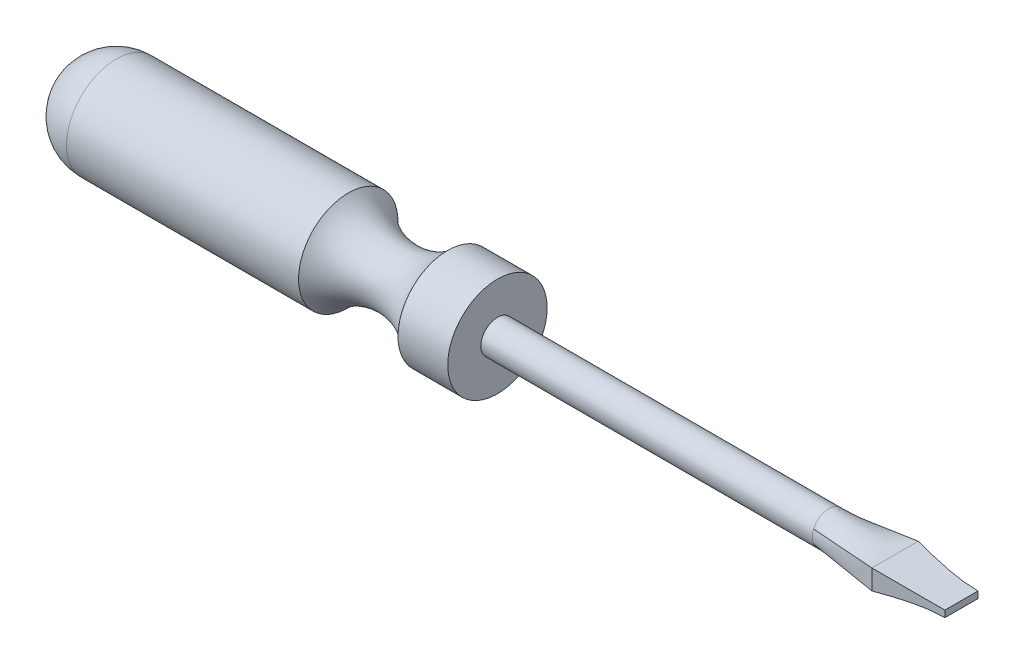
SolidWorks part; units mm, degrees
ref_plane "Front Plane" through (0, 0, 0) normal (1, 0, 0) x (0, 1, 0)
ref_plane "Top Plane" through (0, 0, 0) normal (0, 0, 1) x (0, 1, 0)
ref_plane "Right Plane" through (0, 0, 0) normal (0, 1, 0) x (-1, 0, 0)
sketch "Sketch3" plane through (0, 0, 0) normal (0, 0, 1) x (0, 1, 0)
  line L0 (0, 0) -> (0, 165.1)
  line L1 (19.05, 146.05) -> (19.05, 57.15)
  line L2 (19.05, 19.05) -> (19.05, 0)
  line L3 (19.05, 0) -> (0, 0)
  line L4 (0, 165.1) -> (-19.2923, 165.1) construction
  line L5 (0, 0) -> (0, -127)
  line L6 (0, -127) -> (6.35, -127)
  line L7 (6.35, -127) -> (6.35, 0)
  arc A0 (0, 165.1) -> (19.05, 146.05) centre (0, 146.05) cw
  arc A1 (19.05, 57.15) -> (19.05, 19.05) centre (35.8505, 38.1) ccw
  dimension "D1" = 19.05
  dimension "D4" = 25.4
  dimension "D2" = 38.1
  dimension "D3" = 19.05
  dimension "D5" = 165.1
  dimension "D6" = 6.35
  dimension "D7" = 127
revolve "Revolve2" add sketch "Sketch3" angle 360 about L0 region at (-83.9571, 8.8984, 0)
sketch "Sketch6" plane through (0, 0, 0) normal (1, 0, 0) x (0, 1, 0)
  circle A0 centre (0, 0) radius 19.05 construction
  circle A1 centre (0, 0) radius 19.05
  circle A2 centre (0, 0) radius 6.35
  dimension "D1" = 12.7
ref_plane "Plane3" through (127, 0, 0) normal (1, 0, 0) x (0, 0, -1)
sketch "Sketch7" plane through (127, 0, 0) normal (1, 0, 0) x (0, 0, -1)
  circle A0 centre (0, 0) radius 6.35 construction
  circle A1 centre (0, 0) radius 6.35
  point P3 (0, 0)
ref_plane "Plane1" through (152.4, 0, 0) normal (1, 0, 0) x (0, 0, -1)
ref_plane "Plane2" through (177.8, 0, 0) normal (1, 0, 0) x (0, 0, -1)
sketch "Sketch4" plane through (152.4, 0, 0) normal (1, 0, 0) x (0, 0, -1)
  line L1 (-8.89, 3.81) -> (8.89, 3.81)
  line L2 (-8.89, 3.81) -> (-8.89, -3.81)
  line L3 (-8.89, -3.81) -> (8.89, -3.81)
  line L4 (8.89, 3.81) -> (8.89, -3.81)
  line L5 (-8.89, 3.81) -> (8.89, -3.81) construction
  line L6 (-8.89, -3.81) -> (8.89, 3.81) construction
  circle A2 centre (0, 0) radius 19.05 construction
  circle A3 centre (0, 0) radius 19.05 construction
  point P1 (-0.2403, 7.238)
  point P3 (0, 0)
  point P8 (0, 0)
  point P9 (0, 0)
  point P11 (0, 0)
  point P12 (0, 0)
  point P13 (0, 0)
  dimension "D1" = 7.62
  dimension "D2" = 17.78
sketch "Sketch5" plane through (177.8, 0, 0) normal (1, 0, 0) x (0, 0, -1)
  line L1 (-6.35, -1.27) -> (6.35, -1.27)
  line L2 (-6.35, -1.27) -> (-6.35, 1.27)
  line L3 (-6.35, 1.27) -> (6.35, 1.27)
  line L4 (6.35, -1.27) -> (6.35, 1.27)
  line L5 (-6.35, -1.27) -> (6.35, 1.27) construction
  line L6 (-6.35, 1.27) -> (6.35, -1.27) construction
  point P0 (0, 0)
  point P2 (0, 0)
  dimension "D1" = 12.7
  dimension "D2" = 2.54
extrude "Boss-Extrude1" add sketch "Sketch6" along normal up to vertex (127 mm away) contours A2 region at (0, 0, 0) up to point (127, 0, 0)
loft "Loft5" add profiles "Sketch7", "Sketch4" connector at (127, 0, -6.35) connector at (152.4, 3.81, -8.89)
loft "Loft6" add profiles "Sketch5", "Sketch4<4>" start constraint normal to profile start tangent length 1 connector at (177.8, 1.27, 6.35) connector at (152.4, 3.81, 8.89)
sketch "Sketch4<4>" plane through (152.4, 0, 0) normal (1, 0, 0) x (0, 0, -1) same geometry as "Sketch4"
